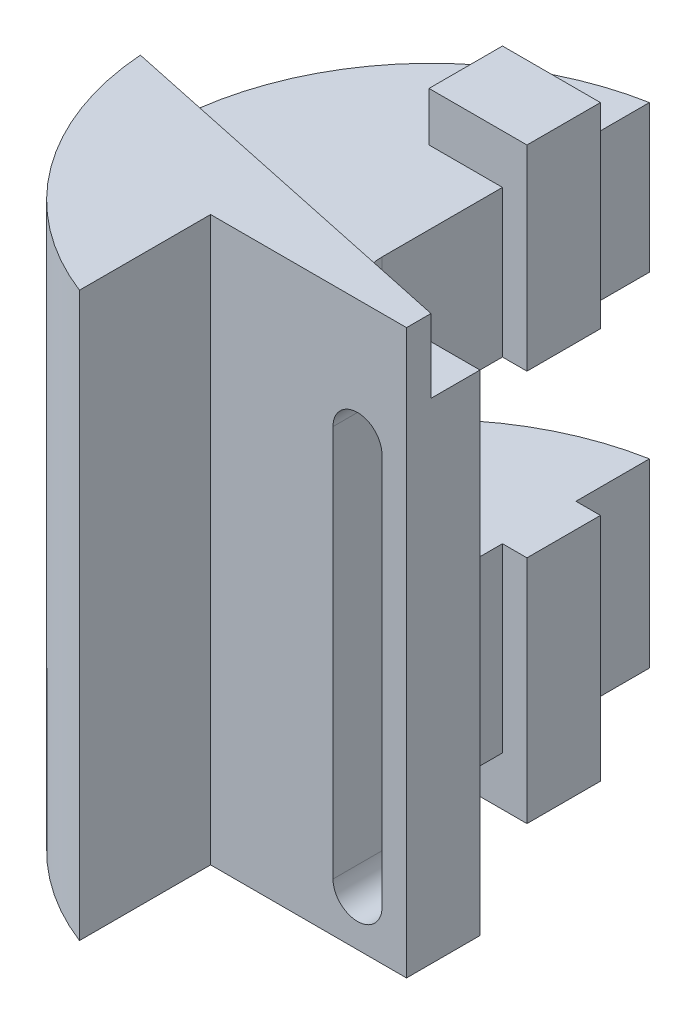
SolidWorks part; units mm, degrees
material "1060 Alloy"
ref_plane "Front Plane" through (0, 0, 0) normal (0, 0, 1) x (1, 0, 0)
ref_plane "Top Plane" through (0, 0, 0) normal (0, 1, 0) x (1, 0, 0)
ref_plane "Right Plane" through (0, 0, 0) normal (1, 0, 0) x (0, 0, -1)
sketch "Sketch1" plane through (0, 0, 0) normal (0, 1, 0) x (1, 0, 0)
  line L0 (-10, 0) -> (-10, 24.5917)
  line L1 (0, -10) -> (20, -10)
  line L2 (-20, -51.7711) -> (-20, -25)
  line L3 (-20, -25) -> (20, -25)
  line L4 (20, -25) -> (20, -10)
  line L5 (-10, 39.5917) -> (-5, 39.5917)
  line L6 (-5, 39.5917) -> (-5, 24.5917)
  line L7 (-5, 24.5917) -> (-10, 24.5917)
  line L8 (-10, 39.5917) -> (-10, 54.5917)
  arc A0 (-10, 54.5917) -> (-20, -51.7711) centre (0, 0) ccw
  arc A1 (-10, 0) -> (0, -10) centre (0, 0) ccw
  dimension "D1" = 111
  dimension "D3" = 15
  dimension "D6" = 15
  dimension "D2" = 10
  dimension "D4" = 40
  dimension "D5" = 20
  dimension "D7" = 5
  dimension "D8" = 15
extrude "Boss-Extrude1" add sketch "Sketch1" along normal blind 100
sketch "Sketch2" plane through (0, 0, 10) normal (0, 0, -1) x (-1, 0, 0)
  line L0 (-9.9954, 90) -> (-9.9954, 10) construction
  line L1 (-4.9954, 90) -> (-4.9954, 10)
  line L2 (-14.9954, 90) -> (-14.9954, 10)
  line L3 (-20, 100) -> (0, 100) construction
  line L5 (-20, 100) -> (-20, 0) construction
  arc A0 (-4.9954, 90) -> (-14.9954, 90) centre (-9.9954, 90) ccw
  arc A1 (-14.9954, 10) -> (-4.9954, 10) centre (-9.9954, 10) ccw
  point P2 (-9.9954, 50)
  dimension "D4" = 5
  dimension "D1" = 80
  dimension "D2" = 10
  dimension "D3" = 10.0046
extrude "Cut-Extrude1" cut sketch "Sketch2" against normal blind 100
sketch "Sketch4" plane through (-5, 0, 0) normal (1, 0, 0) x (0, 0, -1)
  line L0 (54.5917, 100) -> (54.5917, 0) construction
  line L1 (54.5917, 70) -> (14.5917, 70)
  line L2 (54.5917, 70) -> (54.5917, 37)
  line L3 (54.5917, 37) -> (14.5917, 37)
  line L4 (14.5917, 70) -> (14.5917, 37)
  dimension "D1" = 40
  dimension "D2" = 33
  dimension "D3" = 30
extrude "Cut-Extrude2" cut sketch "Sketch4" against normal blind 100
sketch "Sketch5" plane through (0, 100, 0) normal (0, 1, 0) x (1, 0, 0)
  line L0 (20, -20) -> (-55.3569, -3.9824)
  line L1 (20, -25) -> (20, -10) construction
  line L2 (-20, -51.7711) -> (-20, -25) construction
  line L3 (-20, -25) -> (20, -25) construction
  line L4 (20, -25) -> (20, -20)
  line L5 (-20, -51.7711) -> (-20, -25)
  line L6 (-20, -25) -> (20, -25)
  arc A0 (-10, 54.5917) -> (-20, -51.7711) centre (0, 0) ccw construction
  arc A1 (-55.3569, -3.9824) -> (-20, -51.7711) centre (0, 0) ccw
  point P7 (-54.5866, -10)
  point P10 (20, -20)
  dimension "D1" = 5
  dimension "D2" = 78
extrude "Boss-Extrude2" add sketch "Sketch5" along normal blind 15
sketch "Sketch6" plane through (0, 100, 0) normal (0, 1, 0) x (1, 0, 0)
  line L5 (-5, 39.5917) -> (-25, 39.5917)
  line L6 (-5, 39.5917) -> (-5, 24.5917)
  line L7 (-5, 24.5917) -> (-25, 24.5917)
  line L8 (-25, 39.5917) -> (-25, 24.5917)
  dimension "D1" = 15
  dimension "D2" = 20
extrude "Boss-Extrude3" add sketch "Sketch6" along normal blind 10
sketch "Sketch7" plane through (0, 0, 0) normal (0, -1, 0) x (1, 0, 0)
  line L1 (-5, -24.5917) -> (-25, -24.5917)
  line L2 (-5, -24.5917) -> (-5, -39.5917)
  line L3 (-5, -39.5917) -> (-25, -39.5917)
  line L4 (-25, -24.5917) -> (-25, -39.5917)
  dimension "D1" = 15
  dimension "D2" = 20
extrude "Boss-Extrude4" add sketch "Sketch7" along normal blind 10
equation "\"A\"= 55.50mm"
equation "\"B\"= 66mm"
equation "\"C\"= 33mm"
